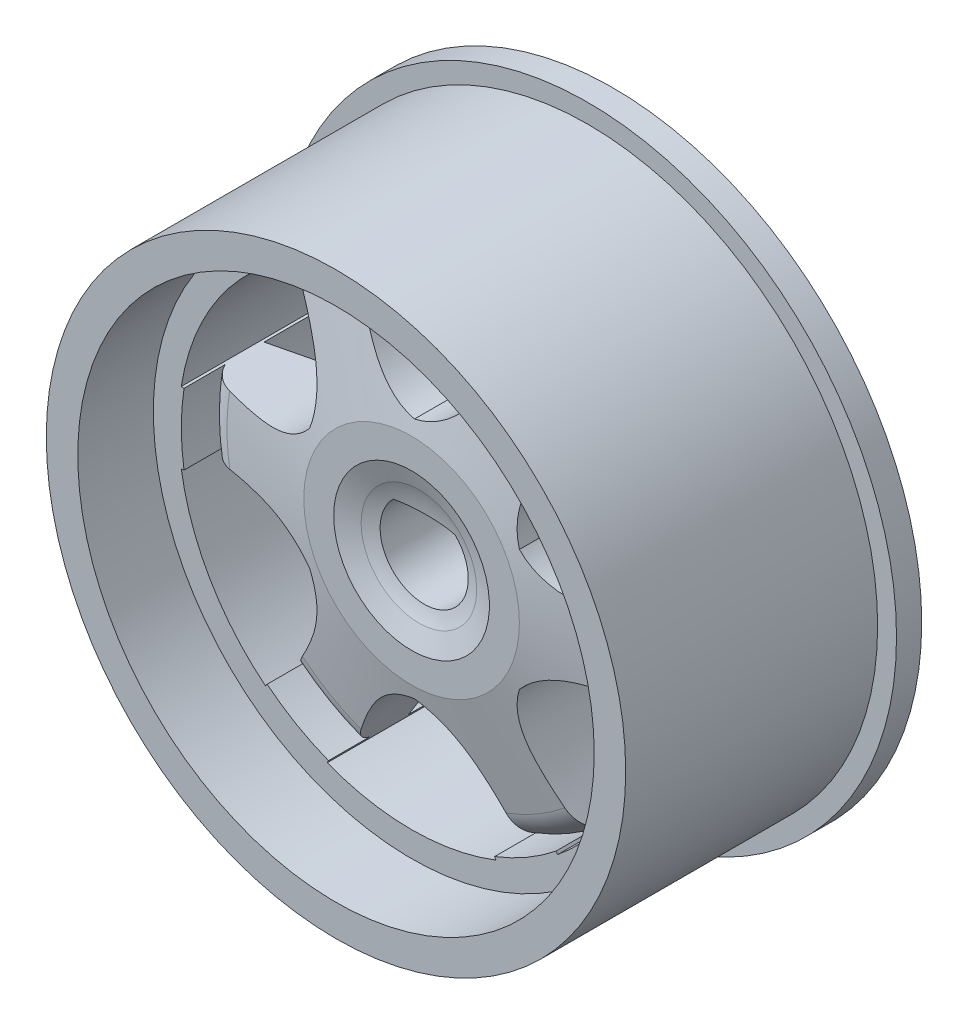
SolidWorks part; units mm, degrees
ref_plane "前视基准面" through (0, 0, 0) normal (0, 0, 1) x (1, 0, 0)
ref_plane "上视基准面" through (0, 0, 0) normal (0, 1, 0) x (1, 0, 0)
ref_plane "右视基准面" through (0, 0, 0) normal (1, 0, 0) x (0, 0, -1)
sketch "草图1" plane through (0, 0, 0) normal (0, 0, 1) x (1, 0, 0)
  line L0 (0, 17.2816) -> (0, -19.4296) construction
  circle A0 centre (0, 0) radius 12.25
  circle A1 centre (0, 0) radius 11.5
  circle A2 centre (0, 0) radius 9.25
  circle A3 centre (0, 0) radius 10.25
  spline S0 degree 3 poles (-3.3468, 8.6233) (-2.6071, 7.1723) (-1.849, 5.142) (0, 4.8082) knots 0 0 0 0 1 1 1 1
  spline S1 degree 3 poles (3.3468, 8.6233) (2.6071, 7.1723) (1.849, 5.142) (0, 4.8082) knots 0 0 0 0 1 1 1 1
  spline S2 degree 3 poles (9.1414, 1.4133) (7.5149, 1.3283) (5.3776, 0.9697) (4.164, 2.4041) knots 0 0 0 0 1 1 1 1
  spline S3 degree 3 poles (5.7946, 7.21) (4.9079, 5.844) (3.5286, 4.1722) (4.164, 2.4041) knots 0 0 0 0 1 1 1 1
  spline S4 degree 3 poles (5.7946, -7.21) (4.9079, -5.844) (3.5286, -4.1722) (4.164, -2.4041) knots 0 0 0 0 1 1 1 1
  spline S5 degree 3 poles (9.1414, -1.4133) (7.5149, -1.3283) (5.3776, -0.9697) (4.164, -2.4041) knots 0 0 0 0 1 1 1 1
  spline S6 degree 3 poles (-3.3468, -8.6233) (-2.6071, -7.1723) (-1.849, -5.142) (0, -4.8082) knots 0 0 0 0 1 1 1 1
  spline S7 degree 3 poles (3.3468, -8.6233) (2.6071, -7.1723) (1.849, -5.142) (0, -4.8082) knots 0 0 0 0 1 1 1 1
  spline S8 degree 3 poles (-9.1414, -1.4133) (-7.5149, -1.3283) (-5.3776, -0.9697) (-4.164, -2.4041) knots 0 0 0 0 1 1 1 1
  spline S9 degree 3 poles (-5.7946, -7.21) (-4.9079, -5.844) (-3.5286, -4.1722) (-4.164, -2.4041) knots 0 0 0 0 1 1 1 1
  spline S10 degree 3 poles (-5.7946, 7.21) (-4.9079, 5.844) (-3.5286, 4.1722) (-4.164, 2.4041) knots 0 0 0 0 1 1 1 1
  spline S11 degree 3 poles (-9.1414, 1.4133) (-7.5149, 1.3283) (-5.3776, 0.9697) (-4.164, 2.4041) knots 0 0 0 0 1 1 1 1
  point P53 (0, 0)
  dimension "D1" = 23
  dimension "D2" = 24.5
  dimension "D3" = 18.5
  dimension "D4" = 20.5
extrude "凸台-拉伸1" add sketch "草图1" along normal blind 11 contours L0 A1 A3 | A1 L0 A3 region at (-10.5071, 0, 0) region at (0.2571, 10.875, 0)
extrude "凸台-拉伸2" add sketch "草图1<3>" along normal blind 1 contours L0 A0 A1 | A0 L0 A1 region at (-11.7739, 0, 0) region at (0.2739, 11.875, 0)
sketch "草图1<3>" plane through (0, 0, 0) normal (0, 0, 1) x (1, 0, 0) same geometry as "草图1"
extrude "凸台-拉伸3" add sketch "草图1<4>" along normal blind 8 contours L0 S0 A2 S10 S11 S8 S9 S6 | L0 A3 A2 | A3 L0 A2 | S1 L0 S7 A2 S4 S5 S2 S3 region at (3.3453, 0, 0) region at (-3.3453, 0, 0) region at (-1.7446, 9.3173, 0) region at (0.2292, 9.75, 0)
sketch "草图1<4>" plane through (0, 0, 0) normal (0, 0, 1) x (1, 0, 0) same geometry as "草图1"
sketch "草图2" plane through (0, 0, 0) normal (0, 1, 0) x (1, 0, 0)
  line L0 (0, 3.2181) -> (0, -13.7135) construction
  line L1 (0, -7.3328) -> (0.6163, -7.3328)
  line L2 (2.2947, -7.7083) -> (3.0898, -8)
  line L3 (-10.25, -8) -> (10.25, -8) construction
  line L4 (3.0898, -8) -> (4.2794, -8)
  line L5 (4.2794, -8) -> (8.2012, -7.1256)
  line L6 (9.1414, -8) -> (9.1414, 0) construction
  line L7 (9.1414, -6.3639) -> (9.1414, -8)
  line L8 (9.1414, -8) -> (4.2794, -8)
  line L9 (3.0898, -8) -> (0, -8)
  line L10 (0, -8) -> (0, -7.3328)
  line L11 (9.1414, 0) -> (9.1414, -4.8233)
  line L12 (9.1414, -4.8233) -> (7.6377, -4.3482)
  line L13 (12.25, 0) -> (-12.25, 0) construction
  line L14 (3.5729, 0) -> (9.1414, 0)
  arc A0 (0.6163, -7.3328) -> (2.2947, -7.7083) centre (0.6163, -11.2723) cw
  arc A1 (8.2012, -7.1256) -> (9.1414, -6.3639) centre (7.9055, -5.7996) ccw
  arc A2 (7.6377, -4.3482) -> (3.5729, 0) centre (9.4647, 1.4338) cw
revolve "切除-旋转2" cut sketch "草图2" angle 360 about L0 region at (6.9064, 0, 1.9146)
sketch "草图3" plane through (0, 0, 0) normal (0, 0, -1) x (-1, 0, 0)
  line L0 (-1.2247, 1.25) -> (1.2247, 1.25)
  arc A0 (-1.2247, 1.25) -> (1.2247, 1.25) centre (0, 0) ccw
  dimension "D1" = 3.5
  dimension "D2" = 1.25
extrude "切除-拉伸1" cut sketch "草图3" against normal up to surface (7.4995 mm away) up to face at (-2.2947, 0, 7.7083)
